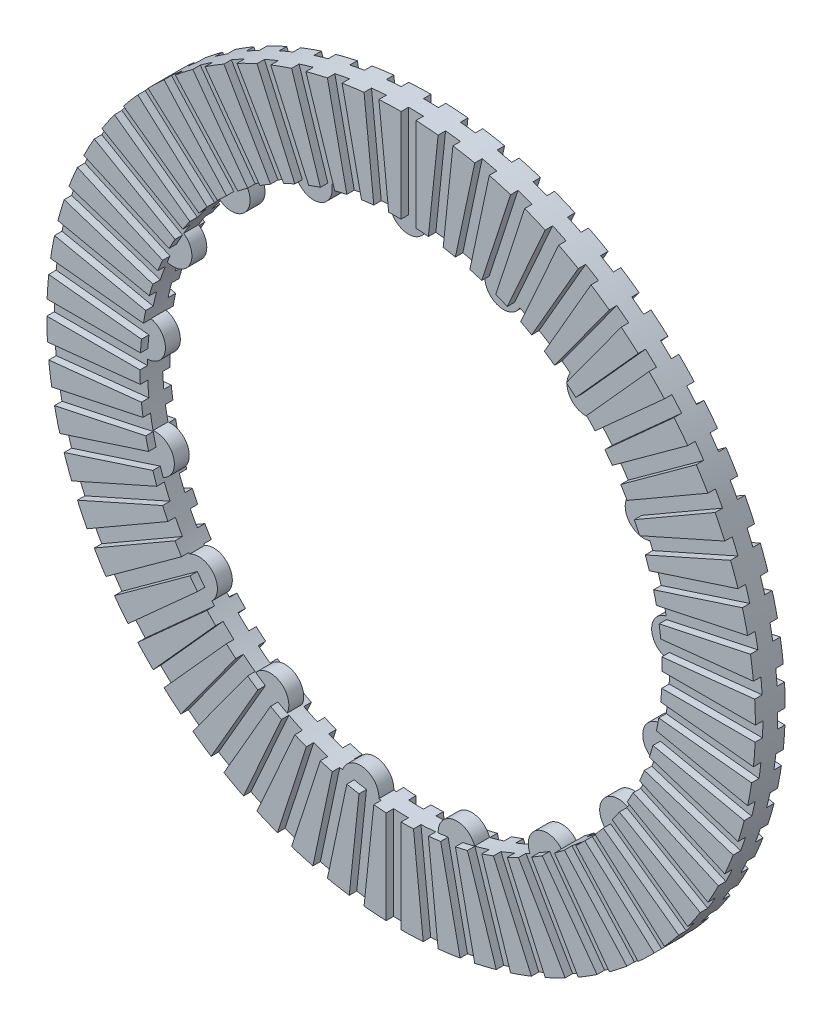
SolidWorks part; units mm, degrees
ref_plane "Front Plane" through (0, 0, 0) normal (0, 0, 1) x (1, 0, 0)
ref_plane "Top Plane" through (0, 0, 0) normal (0, 1, 0) x (1, 0, 0)
ref_plane "Right Plane" through (0, 0, 0) normal (1, 0, 0) x (0, 0, -1)
sketch "Sketch2" plane through (0, 0, 0) normal (0, 0, 1) x (1, 0, 0)
  circle A0 centre (0, 0) radius 47.5
  circle A1 centre (0, 0) radius 35
  dimension "D1" = 95
  dimension "D2" = 70
extrude "Boss-Extrude1" add sketch "Sketch2" along normal blind 4
sketch "Sketch3" plane through (0, 0, 4) normal (0, 0, 1) x (1, 0, 0)
  line L0 (0, 0) -> (47.5, 0)
  circle A0 centre (0, 0) radius 47.5 construction
  point P3 (47.5, 0)
extrude "Cut-Extrude-Thin3" cut sketch "Sketch3" against normal blind 1 and the other way blind 1 thin thin type one direction wall 2
pattern_circular "CirPattern1" count 60 over 360 about axis through (0, 0, 4) along (0, 0, 1) of "Cut-Extrude-Thin3"
ref_plane "Plane1" through (0, 0, 2) normal (0, 0, 1) x (1, 0, 0)
mirror "Mirror1" about plane through (0, 0, 2) normal (0, 0, 1) of "CirPattern1"
sketch "Sketch4" plane through (0, 0, 2) normal (0, 0, 1) x (1, 0, 0)
  circle A0 centre (0, 35.243) radius 2.5
  circle A1 centre (12.7312, 32.8631) radius 2.5
  circle A2 centre (23.743, 26.0449) radius 2.5
  circle A3 centre (31.5482, 15.7091) radius 2.5
  circle A4 centre (35.0926, 3.2518) radius 2.5
  circle A5 centre (33.8976, -9.6447) radius 2.5
  circle A6 centre (28.1245, -21.2386) radius 2.5
  circle A7 centre (18.553, -29.9642) radius 2.5
  circle A8 centre (6.4759, -34.6429) radius 2.5
  circle A9 centre (-6.4759, -34.6429) radius 2.5
  circle A10 centre (-18.553, -29.9642) radius 2.5
  circle A11 centre (-28.1245, -21.2386) radius 2.5
  circle A12 centre (-33.8976, -9.6447) radius 2.5
  circle A13 centre (-35.0926, 3.2518) radius 2.5
  circle A14 centre (-31.5482, 15.7091) radius 2.5
  circle A15 centre (-23.743, 26.0449) radius 2.5
  circle A16 centre (-12.7312, 32.8631) radius 2.5
  point P37 (0, 0)
  dimension "D1" = 5
  dimension "D2" = 17
extrude "Boss-Extrude2" add sketch "Sketch4" along normal blind 1 and the other way blind 1 contours A15 | A16 | A0 | A2 | A1 | A14 | A13 | A12 | A4 | A3 | A5 | A8 | A9 | A10 | A11 | A6 | A7
